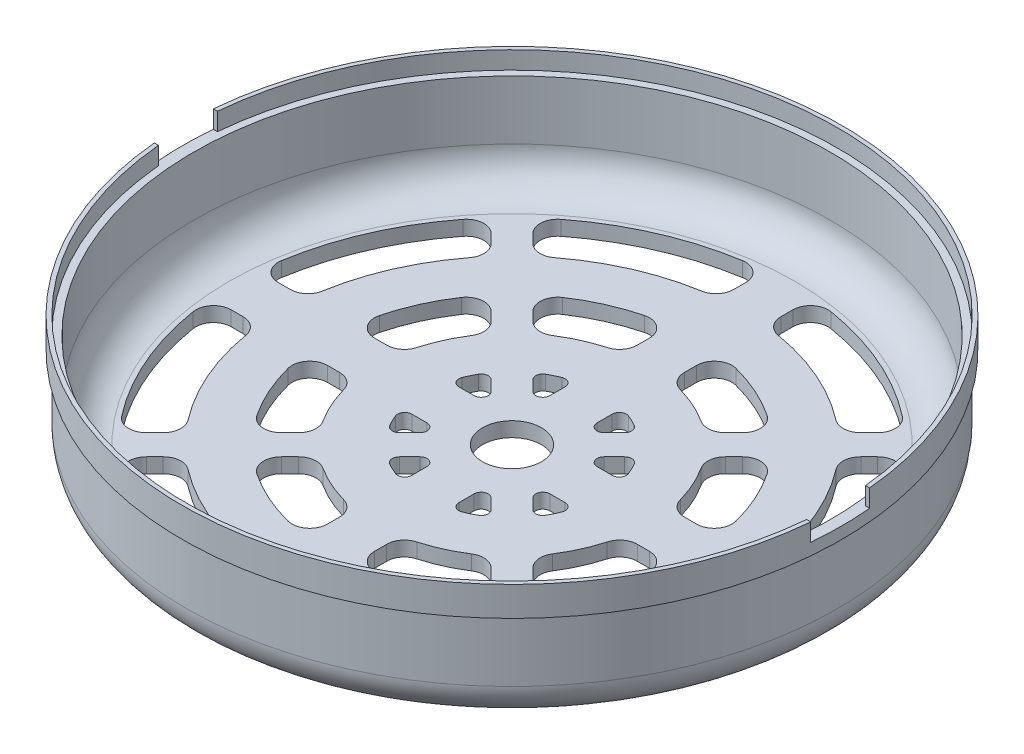
SolidWorks part; units mm, degrees
ref_plane "Front Plane" through (0, 0, 0) normal (0, 0, 1) x (1, 0, 0)
ref_plane "Top Plane" through (0, 0, 0) normal (0, 1, 0) x (1, 0, 0)
ref_plane "Right Plane" through (0, 0, 0) normal (1, 0, 0) x (0, 0, -1)
sketch "Sketch19" plane through (0, 0, 0) normal (0, 1, 0) x (1, 0, 0)
  line L0 (0, 0) -> (17.7862, 0) construction
  line L1 (0, 0) -> (0, 20.3356) construction
  line L2 (773.8577, -773.8577) -> (33.3754, -33.3754) construction
  line L3 (3.5355, -3.5355) -> (-717.8548, 717.8548) construction
  line L4 (11.3153, 7.7797) -> (9.5841, 6.0485)
  line L5 (12.9985, 4) -> (10.4326, 4)
  line L6 (7.7797, 11.3153) -> (6.0485, 9.5841)
  line L7 (-29.2434, 32.779) -> (-27.8176, 31.3532)
  line L8 (-32.779, 29.2434) -> (-31.3532, 27.8176)
  line L9 (-21.3252, 17.7897) -> (-19.8812, 16.3456)
  line L10 (-17.7897, 21.3252) -> (-16.3456, 19.8812)
  line L11 (-7.7797, 11.3153) -> (-6.0485, 9.5841)
  line L12 (-11.3153, 7.7797) -> (-9.5841, 6.0485)
  line L13 (-4, 43.6422) -> (-4, 41.6154)
  line L14 (-4, 27.3174) -> (-4, 25.2476)
  line L15 (-4, 12.9985) -> (-4, 10.4326)
  line L16 (-12.9985, 4) -> (-10.4326, 4)
  line L17 (-27.3174, 4) -> (-25.2476, 4)
  line L18 (-43.6422, 4) -> (-41.6154, 4)
  line L19 (4, 12.9985) -> (4, 10.4326)
  line L20 (4, 27.3174) -> (4, 25.2476)
  line L21 (17.7897, 21.3252) -> (16.3456, 19.8812)
  line L22 (21.3252, 17.7897) -> (19.8812, 16.3456)
  line L23 (27.3174, 4) -> (25.2476, 4)
  line L24 (32.779, 29.2434) -> (31.3532, 27.8176)
  line L25 (43.6422, 4) -> (41.6154, 4)
  line L26 (4, 43.6422) -> (4, 41.6154)
  line L27 (29.2434, 32.779) -> (27.8176, 31.3532)
  line L28 (4, -43.6422) -> (4, -41.6154)
  line L29 (29.2434, -32.779) -> (27.8176, -31.3532)
  line L30 (32.779, -29.2434) -> (31.3532, -27.8176)
  line L31 (43.6422, -4) -> (41.6154, -4)
  line L32 (27.3174, -4) -> (25.2476, -4)
  line L33 (21.3252, -17.7897) -> (19.8812, -16.3456)
  line L34 (12.9985, -4) -> (10.4326, -4)
  line L35 (11.3153, -7.7797) -> (9.5841, -6.0485)
  line L36 (4, -12.9985) -> (4, -10.4326)
  line L37 (7.7797, -11.3153) -> (6.0485, -9.5841)
  line L38 (4, -27.3174) -> (4, -25.2476)
  line L39 (17.7897, -21.3252) -> (16.3456, -19.8812)
  line L40 (-11.3153, -7.7797) -> (-9.5841, -6.0485)
  line L41 (-12.9985, -4) -> (-10.4326, -4)
  line L42 (-7.7797, -11.3153) -> (-6.0485, -9.5841)
  line L43 (-4, -12.9985) -> (-4, -10.4326)
  line L44 (-4, -27.3174) -> (-4, -25.2476)
  line L45 (-17.7897, -21.3252) -> (-16.3456, -19.8812)
  line L46 (-21.3252, -17.7897) -> (-19.8812, -16.3456)
  line L47 (-27.3174, -4) -> (-25.2476, -4)
  line L48 (-32.779, -29.2434) -> (-31.3532, -27.8176)
  line L49 (-43.6422, -4) -> (-41.6154, -4)
  line L50 (-4, -43.6422) -> (-4, -41.6154)
  line L51 (-29.2434, -32.779) -> (-27.8176, -31.3532)
  circle A0 centre (0, 0) radius 55.2
  circle A8 centre (0, 0) radius 5
  arc A9 (-25.9409, 17.3352) -> (-30.2235, 7.7447) centre (0, 0) ccw
  arc A10 (-19.4831, 12.5956) -> (-22.3566, 6.1985) centre (0, 0) ccw
  arc A11 (-37.2691, 28.963) -> (-46.6043, 7.4751) centre (0, 0) ccw
  arc A12 (-31.0948, 23.8695) -> (-38.6569, 6.5024) centre (0, 0) ccw
  arc A13 (-7.4751, 46.6043) -> (-28.963, 37.2691) centre (0, 0) ccw
  arc A14 (-6.5024, 38.6569) -> (-23.8695, 31.0948) centre (0, 0) ccw
  arc A15 (-7.7447, 30.2235) -> (-17.3352, 25.9409) centre (0, 0) ccw
  arc A16 (-6.1985, 22.3566) -> (-12.5956, 19.4831) centre (0, 0) ccw
  arc A17 (-5.6457, 14.1126) -> (-7.5253, 13.2064) centre (0, 0) ccw
  arc A18 (-13.2064, 7.5253) -> (-14.1126, 5.6457) centre (0, 0) ccw
  arc A19 (-22.3566, 6.1985) -> (-25.2476, 4) centre (-25.2476, 7) cw
  arc A20 (-27.3174, 4) -> (-30.2235, 7.7447) centre (-27.3174, 7) cw
  arc A21 (-21.3252, 17.7897) -> (-25.9409, 17.3352) centre (-23.4466, 15.6684) ccw
  arc A22 (-19.8812, 16.3456) -> (-19.4831, 12.5956) centre (-22.0025, 14.2243) cw
  arc A23 (-4, 25.2476) -> (-6.1985, 22.3566) centre (-7, 25.2476) cw
  arc A24 (-16.3456, 19.8812) -> (-12.5956, 19.4831) centre (-14.2243, 22.0025) ccw
  arc A25 (-17.7897, 21.3252) -> (-17.3352, 25.9409) centre (-15.6684, 23.4466) cw
  arc A26 (-4, 27.3174) -> (-7.7447, 30.2235) centre (-7, 27.3174) ccw
  arc A27 (-4, 41.6154) -> (-6.5024, 38.6569) centre (-7, 41.6154) cw
  arc A28 (-4, 43.6422) -> (-7.4751, 46.6043) centre (-7, 43.6422) ccw
  arc A29 (-29.2434, 32.779) -> (-28.963, 37.2691) centre (-27.1221, 34.9003) cw
  arc A30 (-27.8176, 31.3532) -> (-23.8695, 31.0948) centre (-25.6963, 33.4745) ccw
  arc A31 (-31.3532, 27.8176) -> (-31.0948, 23.8695) centre (-33.4745, 25.6963) cw
  arc A32 (-38.6569, 6.5024) -> (-41.6154, 4) centre (-41.6154, 7) cw
  arc A33 (-43.6422, 4) -> (-46.6043, 7.4751) centre (-43.6422, 7) cw
  arc A34 (-32.779, 29.2434) -> (-37.2691, 28.963) centre (-34.9003, 27.1221) ccw
  arc A35 (-12.9985, 4) -> (-14.1126, 5.6457) centre (-12.9985, 5.2) cw
  arc A36 (-11.3153, 7.7797) -> (-13.2064, 7.5253) centre (-12.1638, 6.9312) ccw
  arc A37 (-10.4326, 4) -> (-9.5841, 6.0485) centre (-10.4326, 5.2) ccw
  arc A38 (-4, 10.4326) -> (-6.0485, 9.5841) centre (-5.2, 10.4326) cw
  arc A39 (-7.7797, 11.3153) -> (-7.5253, 13.2064) centre (-6.9312, 12.1638) cw
  arc A40 (-4, 12.9985) -> (-5.6457, 14.1126) centre (-5.2, 12.9985) ccw
  arc A41 (10.4326, 4) -> (9.5841, 6.0485) centre (10.4326, 5.2) cw
  arc A42 (12.9985, 4) -> (14.1126, 5.6457) centre (12.9985, 5.2) ccw
  arc A43 (11.3153, 7.7797) -> (13.2064, 7.5253) centre (12.1638, 6.9312) cw
  arc A44 (13.2064, 7.5253) -> (14.1126, 5.6457) centre (0, 0) cw
  arc A45 (5.6457, 14.1126) -> (7.5253, 13.2064) centre (0, 0) cw
  arc A46 (7.7797, 11.3153) -> (7.5253, 13.2064) centre (6.9312, 12.1638) ccw
  arc A47 (4, 10.4326) -> (6.0485, 9.5841) centre (5.2, 10.4326) ccw
  arc A48 (4, 12.9985) -> (5.6457, 14.1126) centre (5.2, 12.9985) cw
  arc A49 (7.7447, 30.2235) -> (17.3352, 25.9409) centre (0, 0) cw
  arc A50 (4, 27.3174) -> (7.7447, 30.2235) centre (7, 27.3174) cw
  arc A51 (4, 25.2476) -> (6.1985, 22.3566) centre (7, 25.2476) ccw
  arc A52 (6.1985, 22.3566) -> (12.5956, 19.4831) centre (0, 0) cw
  arc A53 (16.3456, 19.8812) -> (12.5956, 19.4831) centre (14.2243, 22.0025) cw
  arc A54 (17.7897, 21.3252) -> (17.3352, 25.9409) centre (15.6684, 23.4466) ccw
  arc A55 (19.8812, 16.3456) -> (19.4831, 12.5956) centre (22.0025, 14.2243) ccw
  arc A56 (19.4831, 12.5956) -> (22.3566, 6.1985) centre (0, 0) cw
  arc A57 (22.3566, 6.1985) -> (25.2476, 4) centre (25.2476, 7) ccw
  arc A58 (27.3174, 4) -> (30.2235, 7.7447) centre (27.3174, 7) ccw
  arc A59 (21.3252, 17.7897) -> (25.9409, 17.3352) centre (23.4466, 15.6684) cw
  arc A60 (25.9409, 17.3352) -> (30.2235, 7.7447) centre (0, 0) cw
  arc A61 (37.2691, 28.963) -> (46.6043, 7.4751) centre (0, 0) cw
  arc A62 (32.779, 29.2434) -> (37.2691, 28.963) centre (34.9003, 27.1221) cw
  arc A63 (31.3532, 27.8176) -> (31.0948, 23.8695) centre (33.4745, 25.6963) ccw
  arc A64 (31.0948, 23.8695) -> (38.6569, 6.5024) centre (0, 0) cw
  arc A65 (38.6569, 6.5024) -> (41.6154, 4) centre (41.6154, 7) ccw
  arc A66 (43.6422, 4) -> (46.6043, 7.4751) centre (43.6422, 7) ccw
  arc A67 (7.4751, 46.6043) -> (28.963, 37.2691) centre (0, 0) cw
  arc A68 (4, 43.6422) -> (7.4751, 46.6043) centre (7, 43.6422) cw
  arc A69 (4, 41.6154) -> (6.5024, 38.6569) centre (7, 41.6154) ccw
  arc A70 (6.5024, 38.6569) -> (23.8695, 31.0948) centre (0, 0) cw
  arc A71 (29.2434, 32.779) -> (28.963, 37.2691) centre (27.1221, 34.9003) ccw
  arc A72 (27.8176, 31.3532) -> (23.8695, 31.0948) centre (25.6963, 33.4745) cw
  arc A73 (4, -43.6422) -> (7.4751, -46.6043) centre (7, -43.6422) ccw
  arc A74 (4, -41.6154) -> (6.5024, -38.6569) centre (7, -41.6154) cw
  arc A75 (6.5024, -38.6569) -> (23.8695, -31.0948) centre (0, 0) ccw
  arc A76 (27.8176, -31.3532) -> (23.8695, -31.0948) centre (25.6963, -33.4745) ccw
  arc A77 (29.2434, -32.779) -> (28.963, -37.2691) centre (27.1221, -34.9003) cw
  arc A78 (7.4751, -46.6043) -> (28.963, -37.2691) centre (0, 0) ccw
  arc A79 (32.779, -29.2434) -> (37.2691, -28.963) centre (34.9003, -27.1221) ccw
  arc A80 (31.3532, -27.8176) -> (31.0948, -23.8695) centre (33.4745, -25.6963) cw
  arc A81 (31.0948, -23.8695) -> (38.6569, -6.5024) centre (0, 0) ccw
  arc A82 (38.6569, -6.5024) -> (41.6154, -4) centre (41.6154, -7) cw
  arc A83 (43.6422, -4) -> (46.6043, -7.4751) centre (43.6422, -7) cw
  arc A84 (37.2691, -28.963) -> (46.6043, -7.4751) centre (0, 0) ccw
  arc A85 (21.3252, -17.7897) -> (25.9409, -17.3352) centre (23.4466, -15.6684) ccw
  arc A86 (25.9409, -17.3352) -> (30.2235, -7.7447) centre (0, 0) ccw
  arc A87 (27.3174, -4) -> (30.2235, -7.7447) centre (27.3174, -7) cw
  arc A88 (22.3566, -6.1985) -> (25.2476, -4) centre (25.2476, -7) cw
  arc A89 (19.4831, -12.5956) -> (22.3566, -6.1985) centre (0, 0) ccw
  arc A90 (19.8812, -16.3456) -> (19.4831, -12.5956) centre (22.0025, -14.2243) cw
  arc A91 (11.3153, -7.7797) -> (13.2064, -7.5253) centre (12.1638, -6.9312) ccw
  arc A92 (13.2064, -7.5253) -> (14.1126, -5.6457) centre (0, 0) ccw
  arc A93 (12.9985, -4) -> (14.1126, -5.6457) centre (12.9985, -5.2) cw
  arc A94 (10.4326, -4) -> (9.5841, -6.0485) centre (10.4326, -5.2) ccw
  arc A95 (4, -12.9985) -> (5.6457, -14.1126) centre (5.2, -12.9985) ccw
  arc A96 (4, -10.4326) -> (6.0485, -9.5841) centre (5.2, -10.4326) cw
  arc A97 (7.7797, -11.3153) -> (7.5253, -13.2064) centre (6.9312, -12.1638) cw
  arc A98 (5.6457, -14.1126) -> (7.5253, -13.2064) centre (0, 0) ccw
  arc A99 (4, -27.3174) -> (7.7447, -30.2235) centre (7, -27.3174) ccw
  arc A100 (4, -25.2476) -> (6.1985, -22.3566) centre (7, -25.2476) cw
  arc A101 (6.1985, -22.3566) -> (12.5956, -19.4831) centre (0, 0) ccw
  arc A102 (16.3456, -19.8812) -> (12.5956, -19.4831) centre (14.2243, -22.0025) ccw
  arc A103 (17.7897, -21.3252) -> (17.3352, -25.9409) centre (15.6684, -23.4466) cw
  arc A104 (7.7447, -30.2235) -> (17.3352, -25.9409) centre (0, 0) ccw
  arc A105 (-10.4326, -4) -> (-9.5841, -6.0485) centre (-10.4326, -5.2) cw
  arc A106 (-12.9985, -4) -> (-14.1126, -5.6457) centre (-12.9985, -5.2) ccw
  arc A107 (-11.3153, -7.7797) -> (-13.2064, -7.5253) centre (-12.1638, -6.9312) cw
  arc A108 (-13.2064, -7.5253) -> (-14.1126, -5.6457) centre (0, 0) cw
  arc A109 (-5.6457, -14.1126) -> (-7.5253, -13.2064) centre (0, 0) cw
  arc A110 (-7.7797, -11.3153) -> (-7.5253, -13.2064) centre (-6.9312, -12.1638) ccw
  arc A111 (-4, -10.4326) -> (-6.0485, -9.5841) centre (-5.2, -10.4326) ccw
  arc A112 (-4, -12.9985) -> (-5.6457, -14.1126) centre (-5.2, -12.9985) cw
  arc A113 (-7.7447, -30.2235) -> (-17.3352, -25.9409) centre (0, 0) cw
  arc A114 (-4, -27.3174) -> (-7.7447, -30.2235) centre (-7, -27.3174) cw
  arc A115 (-4, -25.2476) -> (-6.1985, -22.3566) centre (-7, -25.2476) ccw
  arc A116 (-6.1985, -22.3566) -> (-12.5956, -19.4831) centre (0, 0) cw
  arc A117 (-16.3456, -19.8812) -> (-12.5956, -19.4831) centre (-14.2243, -22.0025) cw
  arc A118 (-17.7897, -21.3252) -> (-17.3352, -25.9409) centre (-15.6684, -23.4466) ccw
  arc A119 (-19.8812, -16.3456) -> (-19.4831, -12.5956) centre (-22.0025, -14.2243) ccw
  arc A120 (-19.4831, -12.5956) -> (-22.3566, -6.1985) centre (0, 0) cw
  arc A121 (-22.3566, -6.1985) -> (-25.2476, -4) centre (-25.2476, -7) ccw
  arc A122 (-27.3174, -4) -> (-30.2235, -7.7447) centre (-27.3174, -7) ccw
  arc A123 (-21.3252, -17.7897) -> (-25.9409, -17.3352) centre (-23.4466, -15.6684) cw
  arc A124 (-25.9409, -17.3352) -> (-30.2235, -7.7447) centre (0, 0) cw
  arc A125 (-37.2691, -28.963) -> (-46.6043, -7.4751) centre (0, 0) cw
  arc A126 (-32.779, -29.2434) -> (-37.2691, -28.963) centre (-34.9003, -27.1221) cw
  arc A127 (-31.3532, -27.8176) -> (-31.0948, -23.8695) centre (-33.4745, -25.6963) ccw
  arc A128 (-31.0948, -23.8695) -> (-38.6569, -6.5024) centre (0, 0) cw
  arc A129 (-38.6569, -6.5024) -> (-41.6154, -4) centre (-41.6154, -7) ccw
  arc A130 (-43.6422, -4) -> (-46.6043, -7.4751) centre (-43.6422, -7) ccw
  arc A131 (-7.4751, -46.6043) -> (-28.963, -37.2691) centre (0, 0) cw
  arc A132 (-4, -43.6422) -> (-7.4751, -46.6043) centre (-7, -43.6422) cw
  arc A133 (-4, -41.6154) -> (-6.5024, -38.6569) centre (-7, -41.6154) ccw
  arc A134 (-6.5024, -38.6569) -> (-23.8695, -31.0948) centre (0, 0) cw
  arc A135 (-29.2434, -32.779) -> (-28.963, -37.2691) centre (-27.1221, -34.9003) ccw
  arc A136 (-27.8176, -31.3532) -> (-23.8695, -31.0948) centre (-25.6963, -33.4745) cw
  dimension "D1" = 110.4
  dimension "D3" = 4
  dimension "D4" = 4
  dimension "D5" = 4
  dimension "D6" = 4
  dimension "D7" = 8
  dimension "D8" = 8
  dimension "D9" = 8
  dimension "D10" = 8
  dimension "D11" = 8
  dimension "D14" = 8
  dimension "D15" = 8
  dimension "D16" = 8
  dimension "D17" = 8
  dimension "D18" = 3
  dimension "D19" = 1.2
  dimension "D20" = 10
  dimension "D2" = 45
  dimension "D12" = 2.5
  dimension "D13" = 2.5
extrude "Boss-Extrude1" add sketch "Sketch19" along normal blind 2.5
sketch "Sketch20" plane through (0, 2.5, 0) normal (0, 1, 0) x (1, 0, 0)
  circle A0 centre (0, 0) radius 55.2
  circle A1 centre (0, 0) radius 54
  dimension "D1" = 110.4
  dimension "D2" = 108
extrude "Boss-Extrude2" add sketch "Sketch20" along normal blind 16
fillet "Fillet1" radius 6 2 edges at (0, 2.5, 54) (0, 0, 55.2)
sketch "Sketch21" plane through (0, 18.5, 0) normal (0, 1, 0) x (1, 0, 0)
  circle A0 centre (0, 0) radius 55.9
  circle A1 centre (0, 0) radius 55.2
  dimension "D1" = 111.8
  dimension "D2" = 110.4
extrude "Boss-Extrude3" add sketch "Sketch21" along normal blind 3
sketch "Sketch22" plane through (0, 18.5, 0) normal (0, -1, 0) x (1, 0, 0)
  circle A0 centre (0, 0) radius 55.9
  circle A1 centre (0, 0) radius 54
  dimension "D1" = 111.8
  dimension "D2" = 108
extrude "Boss-Extrude4" add sketch "Sketch22" along normal blind 2
sketch "Sketch23" plane through (0, 18.5, 0) normal (0, 1, 0) x (1, 0, 0)
  line L1 (-102.8889, 5) -> (102.8889, 5)
  line L2 (-102.8889, 5) -> (-102.8889, -5)
  line L3 (-102.8889, -5) -> (102.8889, -5)
  line L4 (102.8889, 5) -> (102.8889, -5)
  line L5 (-102.8889, 5) -> (102.8889, -5) construction
  line L6 (-102.8889, -5) -> (102.8889, 5) construction
  point P0 (0, 0)
  dimension "D1" = 10
  dimension "D2" = 205.7778
extrude "Cut-Extrude1" cut sketch "Sketch23" along normal blind 4
